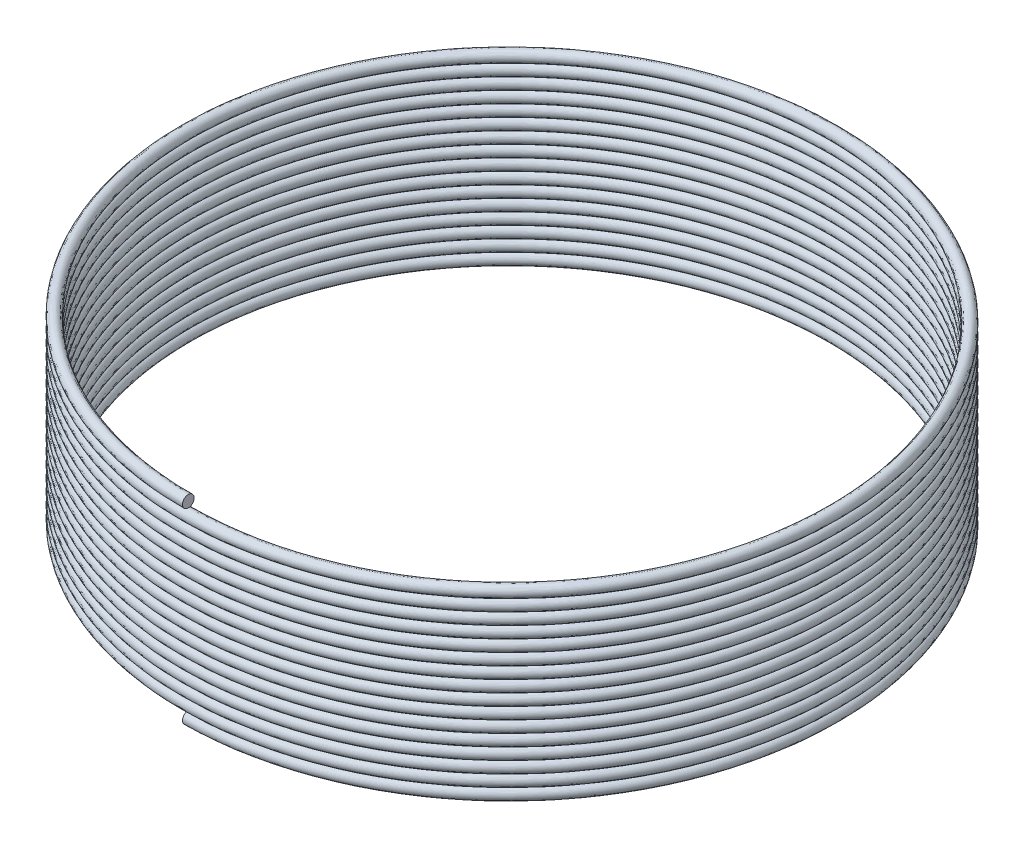
SolidWorks part; units mm, degrees
material "Beryllium Copper, UNS C17200"
ref_plane "Front Plane" through (0, 0, 0) normal (0, 0, 1) x (1, 0, 0)
ref_plane "Top Plane" through (0, 0, 0) normal (0, 1, 0) x (1, 0, 0)
ref_plane "Right Plane" through (0, 0, 0) normal (1, 0, 0) x (0, 0, -1)
sketch "Center Axis" plane through (0, 0, 0) normal (1, 0, 0) x (0, 0, -1)
  line L0 (0, 0) -> (0, 49.506) construction
sketch "Diameter Stowed" plane through (0, 0, 0) normal (0, 1, 0) x (1, 0, 0)
  circle A0 centre (0, 0) radius 22.495
  dimension "D1" = 44.99
sketch "Diameter Deployed" [suppressed] plane through (0, 0, 0) normal (0, 1, 0) x (1, 0, 0)
  circle A0 centre (0, 0) radius 20.405
  dimension "D1" = 40.81
sketch "Wire Gauge XZ" plane through (0, 0, 0) normal (0, 1, 0) x (1, 0, 0)
  circle A0 centre (0, 0) radius 0.405
  dimension "D1" = 0.81
sketch "Wire Gauge YZ" plane through (0, 0, 0) normal (1, 0, 0) x (0, 0, -1)
  line L0 (0.405, 0) -> (-0.405, 0) construction
  line L1 (0, 0) -> (-0.405, 0) construction
  circle A0 centre (0, 0) radius 0.405
curve "Deployed Helix" [suppressed] pitch 31.75 height 508 turns 16
curve "Stowed Helix" pitch 0.8125 height 13 radius 22.495 centre (0, 0, 0) axis (0, 1, 0) start towards (0, 0, 1)
sketch "Sketch7" [suppressed] plane through (0, 0, 0) normal (1, 0, 0) x (0, 0, -1)
  circle A0 centre (-20.405, 0) radius 0.405
  circle A1 centre (0, 0) radius 0.405 construction
  spline S0 degree 3 poles (-20.405, 0) (-20.405, 0.5207) (-19.7449, 1.5688) (-16.869, 3.1356) (-12.3821, 4.7038) (-6.7126, 6.2716) (-0.4021, 7.8395) (5.9469, 9.4074) (11.7279, 10.9753) (16.3888, 12.5432) (19.4846, 14.1111) (20.7195, 15.679) (19.9755, 17.2469) (17.3239, 18.8148) (13.0177, 20.3827) (7.4683, 21.9506) (1.2056, 23.5185) (-5.1722, 25.0864) (-11.056, 26.6543) (-15.884, 28.2222) (-19.1949, 29.7901) (-20.6727, 31.358) (-20.1761, 32.9259) (-17.7527, 34.4938) (-13.6337, 36.0617) (-8.2127, 37.6296) (-2.0074, 39.1975) (4.3897, 40.7654) (10.3675, 42.3333) (15.3552, 43.9012) (18.8764, 45.4691) (20.5948, 47.037) (20.3464, 48.6049) (18.1547, 50.1728) (14.2293, 51.7407) (8.9448, 53.3086) (2.8061, 54.8765) (-3.6006, 56.4444) (-9.6634, 58.0123) (-14.8034, 59.5802) (-18.5295, 61.1481) (-20.486, 62.716) (-20.486, 64.284) (-18.5295, 65.8519) (-14.8034, 67.4198) (-9.6634, 68.9877) (-3.6006, 70.5556) (2.8061, 72.1235) (8.9448, 73.6914) (14.2293, 75.2593) (18.1547, 76.8272) (20.3464, 78.3951) (20.5948, 79.963) (18.8764, 81.5309) (15.3552, 83.0988) (10.3675, 84.6667) (4.3897, 86.2346) (-2.0074, 87.8025) (-8.2127, 89.3704) (-13.6337, 90.9383) (-17.7527, 92.5062) (-20.1761, 94.0741) (-20.6727, 95.642) (-19.1949, 97.2099) (-15.884, 98.7778) (-11.056, 100.3457) (-5.1722, 101.9136) (1.2056, 103.4815) (7.4683, 105.0494) (13.0177, 106.6173) (17.3239, 108.1852) (19.9755, 109.7531) (20.7195, 111.321) (19.4846, 112.8889) (16.3888, 114.4568) (11.7279, 116.0247) (5.9469, 117.5926) (-0.4021, 119.1605) (-6.7126, 120.7284) (-12.3821, 122.2963) (-16.869, 123.8642) (-19.7449, 125.4321) (-20.735, 127) (-19.7449, 128.5679) (-16.869, 130.1358) (-12.3821, 131.7037) (-6.7126, 133.2716) (-0.4021, 134.8395) (5.9469, 136.4074) (11.7279, 137.9753) (16.3888, 139.5432) (19.4846, 141.1111) (20.7195, 142.679) (19.9755, 144.2469) (17.3239, 145.8148) (13.0177, 147.3827) (7.4683, 148.9506) (1.2056, 150.5185) (-5.1722, 152.0864) (-11.056, 153.6543) (-15.884, 155.2222) (-19.1949, 156.7901) (-20.6727, 158.358) (-20.1761, 159.9259) (-17.7527, 161.4938) (-13.6337, 163.0617) (-8.2127, 164.6296) (-2.0074, 166.1975) (4.3897, 167.7654) (10.3675, 169.3333) (15.3552, 170.9012) (18.8764, 172.4691) (20.5948, 174.037) (20.3464, 175.6049) (18.1547, 177.1728) (14.2293, 178.7407) (8.9448, 180.3086) (2.8061, 181.8765) (-3.6006, 183.4444) (-9.6634, 185.0123) (-14.8034, 186.5802) (-18.5295, 188.1481) (-20.486, 189.716) (-20.486, 191.284) (-18.5295, 192.8519) (-14.8034, 194.4198) (-9.6634, 195.9877) (-3.6006, 197.5556) (2.8061, 199.1235) (8.9448, 200.6914) (14.2293, 202.2593) (18.1547, 203.8272) (20.3464, 205.3951) (20.5948, 206.963) (18.8764, 208.5309) (15.3552, 210.0988) (10.3675, 211.6667) (4.3897, 213.2346) (-2.0074, 214.8025) (-8.2127, 216.3704) (-13.6337, 217.9383) (-17.7527, 219.5062) (-20.1761, 221.0741) (-20.6727, 222.642) (-19.1949, 224.2099) (-15.884, 225.7778) (-11.056, 227.3457) (-5.1722, 228.9136) (1.2056, 230.4815) (7.4683, 232.0494) (13.0177, 233.6173) (17.3239, 235.1852) (19.9755, 236.7531) (20.7195, 238.321) (19.4846, 239.8889) (16.3888, 241.4568) (11.7279, 243.0247) (5.9469, 244.5926) (-0.4021, 246.1605) (-6.7126, 247.7284) (-12.3821, 249.2963) (-16.869, 250.8642) (-19.7449, 252.4321) (-20.735, 254) (-19.7449, 255.5679) (-16.869, 257.1358) (-12.3821, 258.7037) (-6.7126, 260.2716) (-0.4021, 261.8395) (5.9469, 263.4074) (11.7279, 264.9753) (16.3888, 266.5432) (19.4846, 268.1111) (20.7195, 269.679) (19.9755, 271.2469) (17.3239, 272.8148) (13.0177, 274.3827) (7.4683, 275.9506) (1.2056, 277.5185) (-5.1722, 279.0864) (-11.056, 280.6543) (-15.884, 282.2222) (-19.1949, 283.7901) (-20.6727, 285.358) (-20.1761, 286.9259) (-17.7527, 288.4938) (-13.6337, 290.0617) (-8.2127, 291.6296) (-2.0074, 293.1975) (4.3897, 294.7654) (10.3675, 296.3333) (15.3552, 297.9012) (18.8764, 299.4691) (20.5948, 301.037) (20.3464, 302.6049) (18.1547, 304.1728) (14.2293, 305.7407) (8.9448, 307.3086) (2.8061, 308.8765) (-3.6006, 310.4444) (-9.6634, 312.0123) (-14.8034, 313.5802) (-18.5295, 315.1481) (-20.486, 316.716) (-20.486, 318.284) (-18.5295, 319.8519) (-14.8034, 321.4198) (-9.6634, 322.9877) (-3.6006, 324.5556) (2.8061, 326.1235) (8.9448, 327.6914) (14.2293, 329.2593) (18.1547, 330.8272) (20.3464, 332.3951) (20.5948, 333.963) (18.8764, 335.5309) (15.3552, 337.0988) (10.3675, 338.6667) (4.3897, 340.2346) (-2.0074, 341.8025) (-8.2127, 343.3704) (-13.6337, 344.9383) (-17.7527, 346.5062) (-20.1761, 348.0741) (-20.6727, 349.642) (-19.1949, 351.2099) (-15.884, 352.7778) (-11.056, 354.3457) (-5.1722, 355.9136) (1.2056, 357.4815) (7.4683, 359.0494) (13.0177, 360.6173) (17.3239, 362.1852) (19.9755, 363.7531) (20.7195, 365.321) (19.4846, 366.8889) (16.3888, 368.4568) (11.7279, 370.0247) (5.9469, 371.5926) (-0.4021, 373.1605) (-6.7126, 374.7284) (-12.3821, 376.2963) (-16.869, 377.8642) (-19.7449, 379.4321) (-20.735, 381) (-19.7449, 382.5679) (-16.869, 384.1358) (-12.3821, 385.7037) (-6.7126, 387.2716) (-0.4021, 388.8395) (5.9469, 390.4074) (11.7279, 391.9753) (16.3888, 393.5432) (19.4846, 395.1111) (20.7195, 396.679) (19.9755, 398.2469) (17.3239, 399.8148) (13.0177, 401.3827) (7.4683, 402.9506) (1.2056, 404.5185) (-5.1722, 406.0864) (-11.056, 407.6543) (-15.884, 409.2222) (-19.1949, 410.7901) (-20.6727, 412.358) (-20.1761, 413.9259) (-17.7527, 415.4938) (-13.6337, 417.0617) (-8.2127, 418.6296) (-2.0074, 420.1975) (4.3897, 421.7654) (10.3675, 423.3333) (15.3552, 424.9012) (18.8764, 426.4691) (20.5948, 428.037) (20.3464, 429.6049) (18.1547, 431.1728) (14.2293, 432.7407) (8.9448, 434.3086) (2.8061, 435.8765) (-3.6006, 437.4444) (-9.6634, 439.0123) (-14.8034, 440.5802) (-18.5295, 442.1481) (-20.486, 443.716) (-20.486, 445.284) (-18.5295, 446.8519) (-14.8034, 448.4198) (-9.6634, 449.9877) (-3.6006, 451.5556) (2.8061, 453.1235) (8.9448, 454.6914) (14.2293, 456.2593) (18.1547, 457.8272) (20.3464, 459.3951) (20.5948, 460.963) (18.8764, 462.5309) (15.3552, 464.0988) (10.3675, 465.6667) (4.3897, 467.2346) (-2.0074, 468.8025) (-8.2127, 470.3704) (-13.6337, 471.9383) (-17.7527, 473.5062) (-20.1761, 475.0741) (-20.6727, 476.642) (-19.1949, 478.2099) (-15.884, 479.7778) (-11.056, 481.3457) (-5.1722, 482.9136) (1.2056, 484.4815) (7.4683, 486.0494) (13.0177, 487.6173) (17.3239, 489.1852) (19.9755, 490.7531) (20.7195, 492.321) (19.4846, 493.8889) (16.3888, 495.4568) (11.7279, 497.0247) (5.9469, 498.5926) (-0.4021, 500.1605) (-6.7126, 501.7284) (-12.3821, 503.2962) (-16.869, 504.8644) (-19.7449, 506.4312) (-20.405, 507.4793) (-20.405, 508) knots 0 0 0 0 0.003086 0.006173 0.009259 0.012346 0.015432 0.018519 0.021605 0.024691 0.027778 0.030864 0.033951 0.037037 0.040123 0.04321 0.046296 0.049383 0.052469 0.055556 0.058642 0.061728 0.064815 0.067901 0.070988 0.074074 0.07716 0.080247 0.083333 0.08642 0.089506 0.092593 0.095679 0.098765 0.101852 0.104938 0.108025 0.111111 0.114198 0.117284 0.12037 0.123457 0.126543 0.12963 0.132716 0.135802 0.138889 0.141975 0.145062 0.148148 0.151235 0.154321 0.157407 0.160494 0.16358 0.166667 0.169753 0.17284 0.175926 0.179012 0.182099 0.185185 0.188272 0.191358 0.194444 0.197531 0.200617 0.203704 0.20679 0.209877 0.212963 0.216049 0.219136 0.222222 0.225309 0.228395 0.231481 0.234568 0.237654 0.240741 0.243827 0.246914 0.25 0.253086 0.256173 0.259259 0.262346 0.265432 0.268519 0.271605 0.274691 0.277778 0.280864 0.283951 0.287037 0.290123 0.29321 0.296296 0.299383 0.302469 0.305556 0.308642 0.311728 0.314815 0.317901 0.320988 0.324074 0.32716 0.330247 0.333333 0.33642 0.339506 0.342593 0.345679 0.348765 0.351852 0.354938 0.358025 0.361111 0.364198 0.367284 0.37037 0.373457 0.376543 0.37963 0.382716 0.385802 0.388889 0.391975 0.395062 0.398148 0.401235 0.404321 0.407407 0.410494 0.41358 0.416667 0.419753 0.42284 0.425926 0.429012 0.432099 0.435185 0.438272 0.441358 0.444444 0.447531 0.450617 0.453704 0.45679 0.459877 0.462963 0.466049 0.469136 0.472222 0.475309 0.478395 0.481481 0.484568 0.487654 0.490741 0.493827 0.496914 0.5 0.503086 0.506173 0.509259 0.512346 0.515432 0.518519 0.521605 0.524691 0.527778 0.530864 0.533951 0.537037 0.540123 0.54321 0.546296 0.549383 0.552469 0.555556 0.558642 0.561728 0.564815 0.567901 0.570988 0.574074 0.57716 0.580247 0.583333 0.58642 0.589506 0.592593 0.595679 0.598765 0.601852 0.604938 0.608025 0.611111 0.614198 0.617284 0.62037 0.623457 0.626543 0.62963 0.632716 0.635802 0.638889 0.641975 0.645062 0.648148 0.651235 0.654321 0.657407 0.660494 0.66358 0.666667 0.669753 0.67284 0.675926 0.679012 0.682099 0.685185 0.688272 0.691358 0.694444 0.697531 0.700617 0.703704 0.70679 0.709877 0.712963 0.716049 0.719136 0.722222 0.725309 0.728395 0.731481 0.734568 0.737654 0.740741 0.743827 0.746914 0.75 0.753086 0.756173 0.759259 0.762346 0.765432 0.768519 0.771605 0.774691 0.777778 0.780864 0.783951 0.787037 0.790123 0.79321 0.796296 0.799383 0.802469 0.805556 0.808642 0.811728 0.814815 0.817901 0.820988 0.824074 0.82716 0.830247 0.833333 0.83642 0.839506 0.842593 0.845679 0.848765 0.851852 0.854938 0.858025 0.861111 0.864198 0.867284 0.87037 0.873457 0.876543 0.87963 0.882716 0.885802 0.888889 0.891975 0.895062 0.898148 0.901235 0.904321 0.907407 0.910494 0.91358 0.916667 0.919753 0.92284 0.925926 0.929012 0.932099 0.935185 0.938272 0.941358 0.944444 0.947531 0.950617 0.953704 0.95679 0.959877 0.962963 0.966049 0.969136 0.972222 0.975309 0.978395 0.981481 0.984568 0.987654 0.990741 0.993827 0.996914 1 1 1 1 construction
sweep "Deployed" [suppressed] add profiles "Sketch7" path "Deployed Helix"
sketch "Sketch8" plane through (0, 0, 0) normal (1, 0, 0) x (0, 0, -1)
  circle A0 centre (-22.495, 0) radius 0.405
  circle A1 centre (0, 0) radius 0.405 construction
  spline S0 degree 3 poles (-22.495, 0) (-22.495, 0.0129) (-21.8147, 0.0388) (-18.8443, 0.0776) (-14.1896, 0.1164) (-8.2666, 0.1552) (-1.6048, 0.194) (5.2005, 0.2328) (11.541, 0.2716) (16.8499, 0.3104) (20.6528, 0.3493) (22.6096, 0.3881) (22.5456, 0.4269) (20.4664, 0.4657) (16.5579, 0.5045) (11.1694, 0.5433) (4.7826, 0.5821) (-2.0317, 0.6209) (-8.6644, 0.6597) (-14.5227, 0.6985) (-19.0829, 0.7373) (-21.9374, 0.7761) (-22.8312, 0.8149) (-21.6842, 0.8537) (-18.5991, 0.8925) (-13.8516, 0.9313) (-7.866, 0.9701) (-1.1773, 1.009) (5.6166, 1.0478) (11.9085, 1.0866) (17.136, 1.1254) (20.8318, 1.1642) (22.6657, 1.203) (22.4736, 1.2418) (20.2729, 1.2806) (16.2601, 1.3194) (10.7939, 1.3582) (4.363, 1.397) (-2.4579, 1.4358) (-9.0591, 1.4746) (-14.8506, 1.5134) (-19.3147, 1.5522) (-22.0525, 1.591) (-22.8191, 1.6299) (-21.5462, 1.6687) (-18.3474, 1.7075) (-13.5087, 1.7463) (-7.4625, 1.7851) (-0.7494, 1.8239) (6.0308, 1.8627) (12.2718, 1.9015) (17.416, 1.9403) (21.0036, 1.9791) (22.7138, 2.0179) (22.3938, 2.0567) (20.0722, 2.0955) (15.9565, 2.1343) (10.4146, 2.1731) (3.9419, 2.2119) (-2.8833, 2.2507) (-9.4506, 2.2896) (-15.1733, 2.3284) (-19.5398, 2.3672) (-22.1597, 2.406) (-22.799, 2.4448) (-21.4005, 2.4836) (-18.0892, 2.5224) (-13.161, 2.5612) (-7.0565, 2.6) (-0.3212, 2.6388) (6.4428, 2.6776) (12.6308, 2.7164) (17.69, 2.7552) (21.1679, 2.794) (22.7539, 2.8328) (22.3061, 2.8716) (19.8645, 2.9104) (15.6474, 2.9493) (10.0317, 2.9881) (3.5193, 3.0269) (-3.3076, 3.0657) (-9.8388, 3.1045) (-15.4907, 3.1433) (-19.758, 3.1821) (-22.2592, 3.2209) (-22.7709, 3.2597) (-21.2473, 3.2985) (-17.8246, 3.3373) (-12.8087, 3.3761) (-6.6479, 3.4149) (0.1071, 3.4537) (6.8525, 3.4925) (12.9854, 3.5313) (17.9577, 3.5701) (21.3249, 3.609) (22.786, 3.6478) (22.2105, 3.6866) (19.6497, 3.7254) (15.3327, 3.7642) (9.6452, 3.803) (3.0956, 3.8418) (-3.7308, 3.8806) (-10.2236, 3.9194) (-15.8026, 3.9582) (-19.9692, 3.997) (-22.3509, 4.0358) (-22.7348, 4.0746) (-21.0867, 4.1134) (-17.5538, 4.1522) (-12.4519, 4.191) (-6.237, 4.2299) (0.5353, 4.2687) (7.2598, 4.3075) (13.3354, 4.3463) (18.2191, 4.3851) (21.4743, 4.4239) (22.8101, 4.4627) (22.1071, 4.5015) (19.4281, 4.5403) (15.0126, 4.5791) (9.2553, 4.6179) (2.6707, 4.6567) (-4.1526, 4.6955) (-10.6047, 4.7343) (-16.109, 4.7731) (-20.1734, 4.8119) (-22.4347, 4.8507) (-22.6907, 4.8896) (-20.9186, 4.9284) (-17.2768, 4.9672) (-12.0907, 5.006) (-5.8239, 5.0448) (0.9634, 5.0836) (7.6646, 5.1224) (13.6807, 5.1612) (18.474, 5.2) (21.6161, 5.2388) (22.8261, 5.2776) (21.9959, 5.3164) (19.1996, 5.3552) (14.6873, 5.394) (8.8621, 5.4328) (2.2449, 5.4716) (-4.573, 5.5104) (-10.9822, 5.5493) (-16.4097, 5.5881) (-20.3705, 5.6269) (-22.5106, 5.6657) (-22.6386, 5.7045) (-20.7432, 5.7433) (-16.9937, 5.7821) (-11.7253, 5.8209) (-5.4088, 5.8597) (1.3911, 5.8985) (8.0667, 5.9373) (14.0212, 5.9761) (18.7225, 6.0149) (21.7504, 6.0537) (22.8342, 6.0925) (21.877, 6.1313) (18.9644, 6.1701) (14.3568, 6.209) (8.4659, 6.2478) (1.8183, 6.2866) (-4.9918, 6.3254) (-11.3557, 6.3642) (-16.7046, 6.403) (-20.5605, 6.4418) (-22.5786, 6.4806) (-22.5786, 6.5194) (-20.5605, 6.5582) (-16.7046, 6.597) (-11.3557, 6.6358) (-4.9918, 6.6746) (1.8183, 6.7134) (8.4659, 6.7522) (14.3568, 6.791) (18.9644, 6.8299) (21.877, 6.8687) (22.8342, 6.9075) (21.7504, 6.9463) (18.7225, 6.9851) (14.0212, 7.0239) (8.0667, 7.0627) (1.3911, 7.1015) (-5.4088, 7.1403) (-11.7253, 7.1791) (-16.9937, 7.2179) (-20.7432, 7.2567) (-22.6386, 7.2955) (-22.5106, 7.3343) (-20.3705, 7.3731) (-16.4097, 7.4119) (-10.9822, 7.4507) (-4.573, 7.4896) (2.2449, 7.5284) (8.8621, 7.5672) (14.6873, 7.606) (19.1996, 7.6448) (21.9959, 7.6836) (22.8261, 7.7224) (21.6161, 7.7612) (18.474, 7.8) (13.6807, 7.8388) (7.6646, 7.8776) (0.9634, 7.9164) (-5.8239, 7.9552) (-12.0907, 7.994) (-17.2768, 8.0328) (-20.9186, 8.0716) (-22.6907, 8.1104) (-22.4347, 8.1493) (-20.1734, 8.1881) (-16.109, 8.2269) (-10.6047, 8.2657) (-4.1526, 8.3045) (2.6707, 8.3433) (9.2553, 8.3821) (15.0126, 8.4209) (19.4281, 8.4597) (22.1071, 8.4985) (22.8101, 8.5373) (21.4743, 8.5761) (18.2191, 8.6149) (13.3354, 8.6537) (7.2598, 8.6925) (0.5353, 8.7313) (-6.237, 8.7701) (-12.4519, 8.809) (-17.5538, 8.8478) (-21.0867, 8.8866) (-22.7348, 8.9254) (-22.3509, 8.9642) (-19.9692, 9.003) (-15.8026, 9.0418) (-10.2236, 9.0806) (-3.7308, 9.1194) (3.0956, 9.1582) (9.6452, 9.197) (15.3327, 9.2358) (19.6497, 9.2746) (22.2105, 9.3134) (22.786, 9.3522) (21.3249, 9.391) (17.9577, 9.4299) (12.9854, 9.4687) (6.8525, 9.5075) (0.1071, 9.5463) (-6.6479, 9.5851) (-12.8087, 9.6239) (-17.8246, 9.6627) (-21.2473, 9.7015) (-22.7709, 9.7403) (-22.2592, 9.7791) (-19.758, 9.8179) (-15.4907, 9.8567) (-9.8388, 9.8955) (-3.3076, 9.9343) (3.5193, 9.9731) (10.0317, 10.0119) (15.6474, 10.0507) (19.8645, 10.0896) (22.3061, 10.1284) (22.7539, 10.1672) (21.1679, 10.206) (17.69, 10.2448) (12.6308, 10.2836) (6.4428, 10.3224) (-0.3212, 10.3612) (-7.0565, 10.4) (-13.161, 10.4388) (-18.0892, 10.4776) (-21.4005, 10.5164) (-22.799, 10.5552) (-22.1597, 10.594) (-19.5398, 10.6328) (-15.1733, 10.6716) (-9.4506, 10.7104) (-2.8833, 10.7493) (3.9419, 10.7881) (10.4146, 10.8269) (15.9565, 10.8657) (20.0722, 10.9045) (22.3938, 10.9433) (22.7138, 10.9821) (21.0036, 11.0209) (17.416, 11.0597) (12.2718, 11.0985) (6.0308, 11.1373) (-0.7494, 11.1761) (-7.4625, 11.2149) (-13.5087, 11.2537) (-18.3474, 11.2925) (-21.5462, 11.3313) (-22.8191, 11.3701) (-22.0525, 11.409) (-19.3147, 11.4478) (-14.8506, 11.4866) (-9.0591, 11.5254) (-2.4579, 11.5642) (4.363, 11.603) (10.7939, 11.6418) (16.2601, 11.6806) (20.2729, 11.7194) (22.4736, 11.7582) (22.6657, 11.797) (20.8318, 11.8358) (17.136, 11.8746) (11.9085, 11.9134) (5.6166, 11.9522) (-1.1773, 11.991) (-7.866, 12.0299) (-13.8516, 12.0687) (-18.5991, 12.1075) (-21.6842, 12.1463) (-22.8312, 12.1851) (-21.9374, 12.2239) (-19.0829, 12.2627) (-14.5227, 12.3015) (-8.6644, 12.3403) (-2.0317, 12.3791) (4.7826, 12.4179) (11.1694, 12.4567) (16.5579, 12.4955) (20.4664, 12.5343) (22.5456, 12.5731) (22.6096, 12.6119) (20.6528, 12.6507) (16.8499, 12.6896) (11.541, 12.7284) (5.2005, 12.7672) (-1.6048, 12.806) (-8.2666, 12.8448) (-14.1896, 12.8836) (-18.8443, 12.9224) (-21.8147, 12.9612) (-22.495, 12.9871) (-22.495, 13) knots 0 0 0 0 0.002985 0.00597 0.008955 0.01194 0.014925 0.01791 0.020896 0.023881 0.026866 0.029851 0.032836 0.035821 0.038806 0.041791 0.044776 0.047761 0.050746 0.053731 0.056716 0.059701 0.062687 0.065672 0.068657 0.071642 0.074627 0.077612 0.080597 0.083582 0.086567 0.089552 0.092537 0.095522 0.098507 0.101493 0.104478 0.107463 0.110448 0.113433 0.116418 0.119403 0.122388 0.125373 0.128358 0.131343 0.134328 0.137313 0.140299 0.143284 0.146269 0.149254 0.152239 0.155224 0.158209 0.161194 0.164179 0.167164 0.170149 0.173134 0.176119 0.179104 0.18209 0.185075 0.18806 0.191045 0.19403 0.197015 0.2 0.202985 0.20597 0.208955 0.21194 0.214925 0.21791 0.220896 0.223881 0.226866 0.229851 0.232836 0.235821 0.238806 0.241791 0.244776 0.247761 0.250746 0.253731 0.256716 0.259701 0.262687 0.265672 0.268657 0.271642 0.274627 0.277612 0.280597 0.283582 0.286567 0.289552 0.292537 0.295522 0.298507 0.301493 0.304478 0.307463 0.310448 0.313433 0.316418 0.319403 0.322388 0.325373 0.328358 0.331343 0.334328 0.337313 0.340299 0.343284 0.346269 0.349254 0.352239 0.355224 0.358209 0.361194 0.364179 0.367164 0.370149 0.373134 0.376119 0.379104 0.38209 0.385075 0.38806 0.391045 0.39403 0.397015 0.4 0.402985 0.40597 0.408955 0.41194 0.414925 0.41791 0.420896 0.423881 0.426866 0.429851 0.432836 0.435821 0.438806 0.441791 0.444776 0.447761 0.450746 0.453731 0.456716 0.459701 0.462687 0.465672 0.468657 0.471642 0.474627 0.477612 0.480597 0.483582 0.486567 0.489552 0.492537 0.495522 0.498507 0.501493 0.504478 0.507463 0.510448 0.513433 0.516418 0.519403 0.522388 0.525373 0.528358 0.531343 0.534328 0.537313 0.540299 0.543284 0.546269 0.549254 0.552239 0.555224 0.558209 0.561194 0.564179 0.567164 0.570149 0.573134 0.576119 0.579104 0.58209 0.585075 0.58806 0.591045 0.59403 0.597015 0.6 0.602985 0.60597 0.608955 0.61194 0.614925 0.61791 0.620896 0.623881 0.626866 0.629851 0.632836 0.635821 0.638806 0.641791 0.644776 0.647761 0.650746 0.653731 0.656716 0.659701 0.662687 0.665672 0.668657 0.671642 0.674627 0.677612 0.680597 0.683582 0.686567 0.689552 0.692537 0.695522 0.698507 0.701493 0.704478 0.707463 0.710448 0.713433 0.716418 0.719403 0.722388 0.725373 0.728358 0.731343 0.734328 0.737313 0.740299 0.743284 0.746269 0.749254 0.752239 0.755224 0.758209 0.761194 0.764179 0.767164 0.770149 0.773134 0.776119 0.779104 0.78209 0.785075 0.78806 0.791045 0.79403 0.797015 0.8 0.802985 0.80597 0.808955 0.81194 0.814925 0.81791 0.820896 0.823881 0.826866 0.829851 0.832836 0.835821 0.838806 0.841791 0.844776 0.847761 0.850746 0.853731 0.856716 0.859701 0.862687 0.865672 0.868657 0.871642 0.874627 0.877612 0.880597 0.883582 0.886567 0.889552 0.892537 0.895522 0.898507 0.901493 0.904478 0.907463 0.910448 0.913433 0.916418 0.919403 0.922388 0.925373 0.928358 0.931343 0.934328 0.937313 0.940299 0.943284 0.946269 0.949254 0.952239 0.955224 0.958209 0.961194 0.964179 0.967164 0.970149 0.973134 0.976119 0.979104 0.98209 0.985075 0.98806 0.991045 0.99403 0.997015 1 1 1 1 construction
sweep "Stowed" add profiles "Sketch8" path "Stowed Helix"
